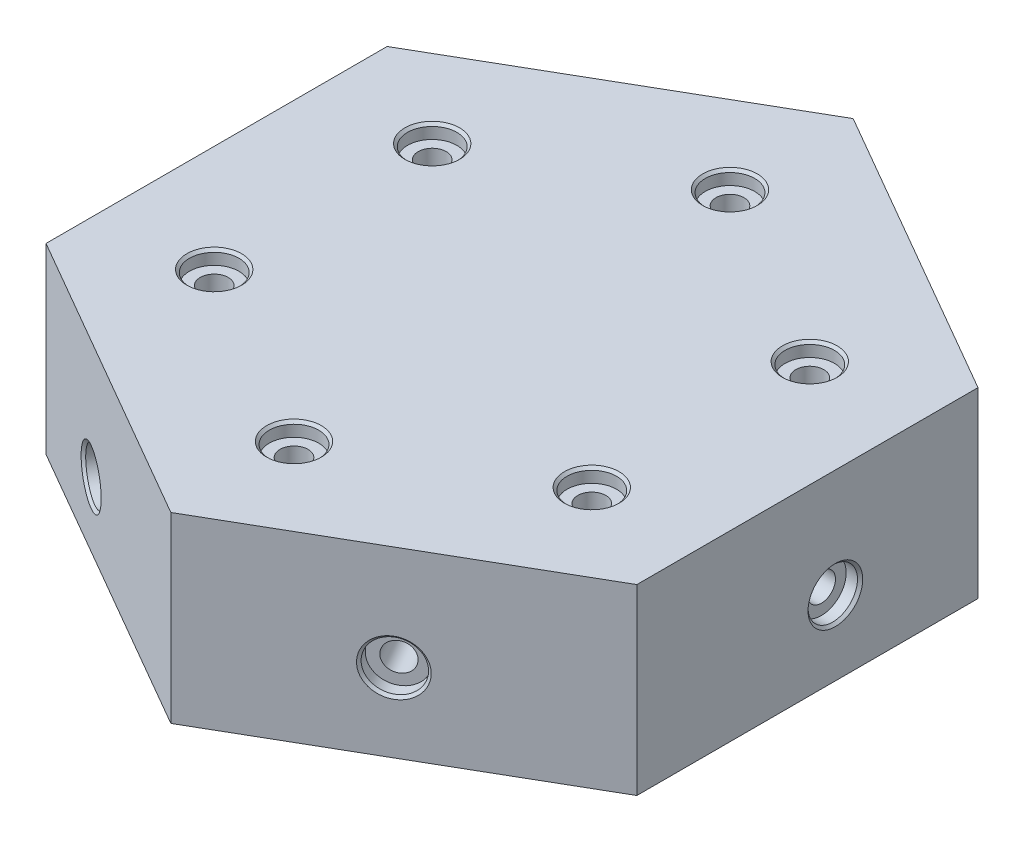
SolidWorks part; units mm, degrees
ref_plane "Front Plane" through (0, 0, 0) normal (0, 0, 1) x (1, 0, 0)
ref_plane "Top Plane" through (0, 0, 0) normal (0, 1, 0) x (1, 0, 0)
ref_plane "Right Plane" through (0, 0, 0) normal (1, 0, 0) x (0, 0, -1)
sketch "Sketch1" plane through (0, 0, 0) normal (0, 1, 0) x (1, 0, 0)
  line L1 (0, 82.1553) -> (-71.1486, 41.0776)
  line L2 (-71.1486, 41.0776) -> (-71.1486, -41.0776)
  line L3 (-71.1486, -41.0776) -> (0, -82.1553)
  line L4 (0, -82.1553) -> (71.1486, -41.0776)
  line L5 (71.1486, -41.0776) -> (71.1486, 41.0776)
  line L6 (71.1486, 41.0776) -> (0, 82.1553)
  circle A0 centre (0, 0) radius 71.1486 construction
extrude "Boss-Extrude1" add sketch "Sketch1" along normal blind 44
sketch "Sketch3" plane through (0, 44, 0) normal (0, 1, 0) x (1, 0, 0)
  line L1 (0, 52.5) -> (-45.4663, 26.25)
  line L2 (-45.4663, 26.25) -> (-45.4663, -26.25)
  line L3 (-45.4663, -26.25) -> (0, -52.5)
  line L4 (0, -52.5) -> (45.4663, -26.25)
  line L5 (45.4663, -26.25) -> (45.4663, 26.25)
  line L6 (45.4663, 26.25) -> (0, 52.5)
  circle A0 centre (0, 0) radius 45.4663 construction
  dimension "D1" = 105
hole_wizard "CBORE for 1/4 Button Head Cap Screw1" positions "3DSketch1" profile "Sketch2" counterbore size "1/4" standard "ANSI Inch"
sketch3d "3DSketch1"
  line L0 (71.1486, 0, -41.0776) -> (0, 44, -82.1553) construction
  point P0 (71.1486, 17.9149, -6.7284)
  point P2 (34.048, 18.8117, 62.4977)
  point P4 (-45.4229, 15.5829, 55.9304)
  point P6 (-71.1486, 19.6856, -1.9569)
  point P8 (-38.2827, 22.2639, -60.0528)
  point P14 (35.5743, 22, -61.6165)
  point P18 (35.5743, 22, -61.6165)
  point P20 (35.5743, 22, -61.6165)
  point P24 (-45.4663, 44, -26.25)
  point P27 (0, 44, -52.5)
  point P30 (45.4663, 44, -26.25)
  point P33 (45.4663, 44, 26.25)
  point P36 (0, 44, 52.5)
  point P39 (-45.4663, 44, 26.25)
sketch "Sketch2" plane through (71.1486, 17.9149, -6.7284) normal (0, 1, 0) x (0, 0, -1)
  line L0 (0, 0) -> (0, 27.0298)
  line L1 (0, 27.0298) -> (3.3782, 25)
  line L2 (3.3782, 25) -> (3.3782, 3.3528)
  line L3 (3.3782, 3.3528) -> (5.9538, 3.3528)
  line L5 (5.9538, 3.3528) -> (5.9538, 0.635)
  line L6 (5.9538, 0.635) -> (6.5888, 0)
  line L7 (6.5888, 0) -> (0, 0)
  line L8 (-5.9538, 0.635) -> (-6.5888, 0) construction
  line L10 (0, 27.0298) -> (-3.3782, 25) construction
  line L11 (0, -6.35) -> (0, 107.95) construction
  dimension "Hole Dia." = 6.7564
  dimension "Hole Depth" = 25
  dimension "C'Bore Dia." = 11.9075
  dimension "C'Bore Depth" = 3.3528
  dimension "Near C'Sink Dia." = 13.1775
  dimension "Near C'Sink Angle" = 90
  dimension "Drill Angle" = 118
